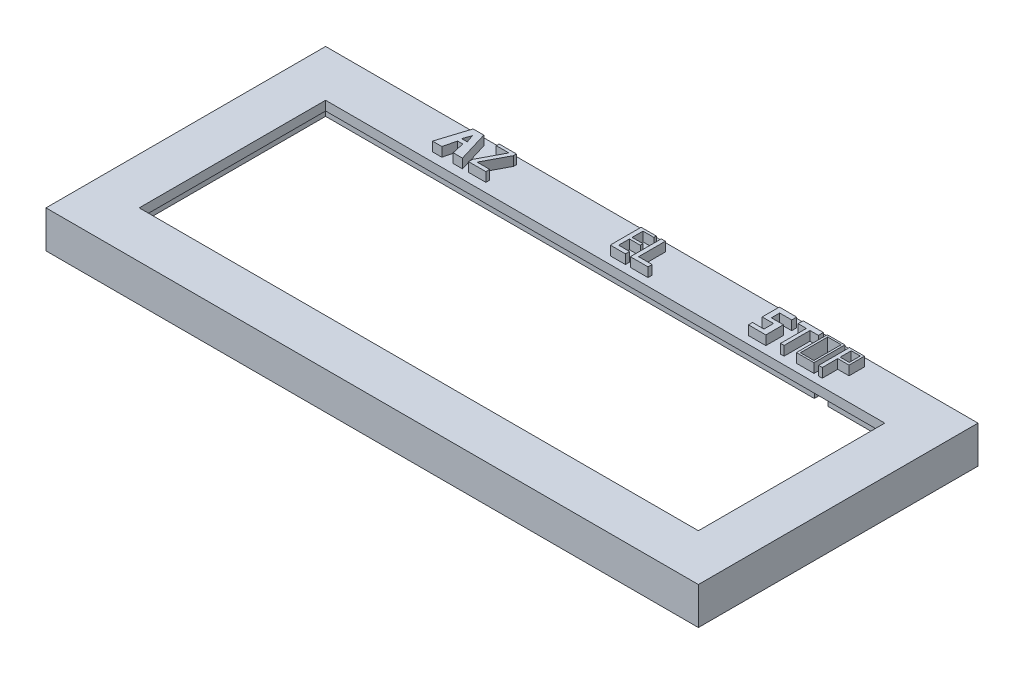
SolidWorks part; units mm, degrees
ref_plane "Alzado" through (0, 0, 0) normal (0, 0, 1) x (1, 0, 0)
ref_plane "Planta" through (0, 0, 0) normal (0, 1, 0) x (1, 0, 0)
ref_plane "Vista lateral" through (0, 0, 0) normal (1, 0, 0) x (0, 0, -1)
sketch "Croquis1" plane through (0, 0, 0) normal (0, 1, 0) x (1, 0, 0)
  line L0 (-382.134, 248.1115) -> (-381.134, 248.1115)
  line L1 (-397.6674, 252.1738) -> (-327.6674, 252.1738)
  line L2 (-397.6674, 252.1738) -> (-397.6674, 222.1738)
  line L3 (-397.6674, 222.1738) -> (-327.6674, 222.1738)
  line L4 (-327.6674, 252.1738) -> (-327.6674, 222.1738)
  line L5 (-392.6674, 247.1738) -> (-332.6674, 247.1738)
  line L6 (-392.6674, 247.1738) -> (-392.6674, 227.1738)
  line L7 (-392.6674, 227.1738) -> (-332.6674, 227.1738)
  line L8 (-332.6674, 247.1738) -> (-332.6674, 227.1738)
  line L9 (-381.134, 248.1115) -> (-380.7959, 249.4629)
  line L10 (-380.7959, 249.4629) -> (-380.2401, 249.4629)
  line L11 (-380.2401, 249.4629) -> (-379.9436, 248.1387)
  line L12 (-379.9436, 248.1387) -> (-378.9436, 248.1387)
  line L13 (-378.9436, 248.1387) -> (-379.9436, 251.4234)
  line L14 (-379.9436, 251.4234) -> (-381.0886, 251.4234)
  line L15 (-381.0886, 251.4234) -> (-382.134, 248.1115)
  line L16 (-380.7959, 249.9048) -> (-380.2014, 249.9048)
  line L17 (-380.2014, 249.9048) -> (-380.4986, 250.7649)
  line L18 (-380.4986, 250.7649) -> (-380.7959, 249.9048)
  line L19 (-378.295, 251.4234) -> (-376.4369, 251.4234)
  line L20 (-376.4369, 251.4234) -> (-376.4369, 251.1114)
  line L21 (-376.4369, 251.1114) -> (-377.7909, 248.5516)
  line L22 (-377.7909, 248.5516) -> (-376.4369, 248.5516)
  line L23 (-376.4369, 248.5516) -> (-376.4369, 248.1387)
  line L24 (-376.4369, 248.1387) -> (-378.295, 248.1387)
  line L25 (-378.295, 248.1387) -> (-378.295, 248.5516)
  line L26 (-378.295, 248.5516) -> (-376.9409, 251.1114)
  line L27 (-376.9409, 251.1114) -> (-378.295, 251.1114)
  line L28 (-378.295, 251.1114) -> (-378.295, 251.4234)
  line L29 (-362.9394, 251.3003) -> (-362.9394, 247.9884)
  line L30 (-362.9394, 247.9884) -> (-361.3109, 247.9884)
  line L31 (-361.3109, 247.9884) -> (-361.3109, 248.4285)
  line L32 (-361.3109, 248.4285) -> (-362.4785, 248.4285)
  line L33 (-362.4785, 248.4285) -> (-362.4785, 249.5842)
  line L34 (-362.4785, 249.5842) -> (-361.3109, 249.5842)
  line L35 (-361.3109, 249.5842) -> (-361.3109, 249.8714)
  line L36 (-361.3109, 249.8714) -> (-362.4785, 249.8714)
  line L37 (-362.4785, 249.8714) -> (-362.4785, 251.0397)
  line L38 (-362.4785, 251.0397) -> (-361.3121, 251.0397)
  line L39 (-361.3121, 251.0397) -> (-361.3121, 251.3003)
  line L40 (-362.9394, 251.3003) -> (-361.3121, 251.3003)
  line L41 (-360.7793, 251.3003) -> (-360.7793, 247.9884)
  line L42 (-360.7793, 247.9884) -> (-358.8906, 247.9884)
  line L43 (-358.8906, 247.9884) -> (-358.8906, 248.4285)
  line L44 (-358.8906, 248.4285) -> (-360.3397, 248.4285)
  line L45 (-360.3397, 248.4285) -> (-360.3397, 251.3003)
  line L46 (-360.3397, 251.3003) -> (-360.7793, 251.3003)
  line L47 (-348.1106, 251.3003) -> (-346.2469, 251.3003)
  line L48 (-346.2469, 251.3003) -> (-346.2469, 250.7649)
  line L49 (-346.2469, 250.7649) -> (-347.5371, 250.7649)
  line L50 (-347.5371, 250.7649) -> (-347.5371, 249.8714)
  line L51 (-347.5371, 249.8714) -> (-346.2469, 249.8714)
  line L52 (-346.2469, 249.8714) -> (-346.2469, 249.4629)
  line L53 (-348.1106, 249.4629) -> (-346.892, 249.4629)
  line L54 (-348.1106, 251.3003) -> (-348.1106, 249.4629)
  line L55 (-346.892, 249.4629) -> (-346.892, 248.4285)
  line L56 (-346.892, 248.4285) -> (-348.1106, 248.4285)
  line L57 (-348.1106, 248.4285) -> (-348.1106, 247.9884)
  line L58 (-348.1106, 247.9884) -> (-346.2469, 247.9884)
  line L59 (-346.2469, 247.9884) -> (-346.2469, 249.4629)
  line L60 (-345.5588, 251.3003) -> (-343.3798, 251.3003)
  line L61 (-343.3798, 251.3003) -> (-343.3798, 250.7649)
  line L62 (-343.3798, 250.7649) -> (-344.2875, 250.7649)
  line L63 (-344.2875, 250.7649) -> (-344.2875, 247.9884)
  line L64 (-344.2875, 247.9884) -> (-344.6701, 247.9884)
  line L65 (-344.6701, 247.9884) -> (-344.6701, 250.7649)
  line L66 (-344.6701, 250.7649) -> (-345.5588, 250.7649)
  line L67 (-345.5588, 250.7649) -> (-345.5588, 251.3003)
  line L68 (-342.9632, 251.3003) -> (-342.9632, 247.9884)
  line L69 (-342.9632, 247.9884) -> (-341.0812, 247.9884)
  line L70 (-341.0812, 247.9884) -> (-341.0812, 251.3003)
  line L71 (-341.0812, 251.3003) -> (-342.9632, 251.3003)
  line L72 (-342.7345, 251.1179) -> (-342.7345, 248.1865)
  line L73 (-342.7345, 248.1865) -> (-341.2884, 248.1865)
  line L74 (-341.2884, 248.1865) -> (-341.2884, 251.1179)
  line L75 (-341.2884, 251.1179) -> (-342.7345, 251.1179)
  line L76 (-340.5833, 251.3003) -> (-340.5833, 247.9884)
  line L77 (-340.5833, 247.9884) -> (-340.1902, 247.9884)
  line L78 (-340.1902, 247.9884) -> (-340.1902, 249.6444)
  line L79 (-340.1902, 249.6444) -> (-338.9775, 249.6444)
  line L80 (-338.9775, 249.6444) -> (-338.9775, 251.3003)
  line L81 (-338.9775, 251.3003) -> (-340.5833, 251.3003)
  line L82 (-340.1902, 251.0948) -> (-340.1902, 249.9048)
  line L83 (-340.1902, 249.9048) -> (-339.2133, 249.9048)
  line L84 (-339.2133, 249.9048) -> (-339.2133, 251.0948)
  line L85 (-339.2133, 251.0948) -> (-340.1902, 251.0948)
  dimension "D1" = 70
  dimension "D2" = 30
  dimension "D3" = 5
  dimension "D4" = 5
  dimension "D5" = 5
  dimension "D6" = 5
  dimension "D7" = 1
  dimension "D8" = 1
extrude "Saliente-Extruir1" add sketch "Croquis1" along normal blind 5 contours L14 L15 L0 L9 L10 L11 L12 L13 L18 L17 L16 | L28 L27 L26 L25 L24 L23 L22 L21 L20 L19 | L40 L29 L30 L31 L32 L33 L34 L35 L36 L37 L38 L39 | L45 L46 L41 L42 L43 L44 | L58 L59 L52 L51 L50 L49 L48 L47 L54 L53 L55 L56 L57 | L70 L71 L68 L69 L75 L74 L73 L72 | L80 L81 L76 L77 L78 L79 L85 L84 L83 L82 | L63 L64 L65 L66 L67 L60 L61 L62 region at (-380.533, 0, -249.6482) region at (-377.3659, 0, -249.7148) region at (-362.1257, 0, -251.2634) region at (-360.5595, 0, -251.2622) region at (-347.1585, 0, -249.672) region at (-342.0222, 0, -251.2622) region at (-339.7804, 0, -251.2635)
extrude "Saliente-Extruir2" add sketch "Croquis1<3>" along normal blind 4 contours L4 L1 L2 L3 L81 L80 L79 L78 L77 L76 L71 L70 L69 L68 L59 L58 L57 L56 L55 L53 L54 L47 L48 L49 L50 L51 L52 L46 L45 L44 L43 L42 L41 L15 L14 L13 L12 L11 L10 L9 L0 L5 L8 L7 L6 region at (-362.6674, 0, -251.4122)
sketch "Croquis1<3>" plane through (0, 0, 0) normal (0, 1, 0) x (1, 0, 0) same geometry as "Croquis1"
sketch "Croquis3" plane through (0, 0, 0) normal (0, -1, 0) x (1, 0, 0)
  line L0 (-397.6674, -252.1738) -> (-327.6674, -252.1738) construction
  line L1 (-395.1674, -224.6738) -> (-330.1674, -224.6738)
  line L2 (-395.1674, -224.6738) -> (-395.1674, -249.6738)
  line L3 (-395.1674, -249.6738) -> (-330.1674, -249.6738)
  line L4 (-330.1674, -224.6738) -> (-330.1674, -249.6738)
  line L5 (-397.6674, -222.1738) -> (-327.6674, -222.1738) construction
  line L6 (-327.6674, -252.1738) -> (-327.6674, -222.1738) construction
  line L7 (-397.6674, -252.1738) -> (-397.6674, -222.1738) construction
  dimension "D1" = 2.5
  dimension "D2" = 2.5
  dimension "D3" = 2.5
  dimension "D4" = 2.5
extrude "Cortar-Extruir1" cut sketch "Croquis3" against normal blind 3
